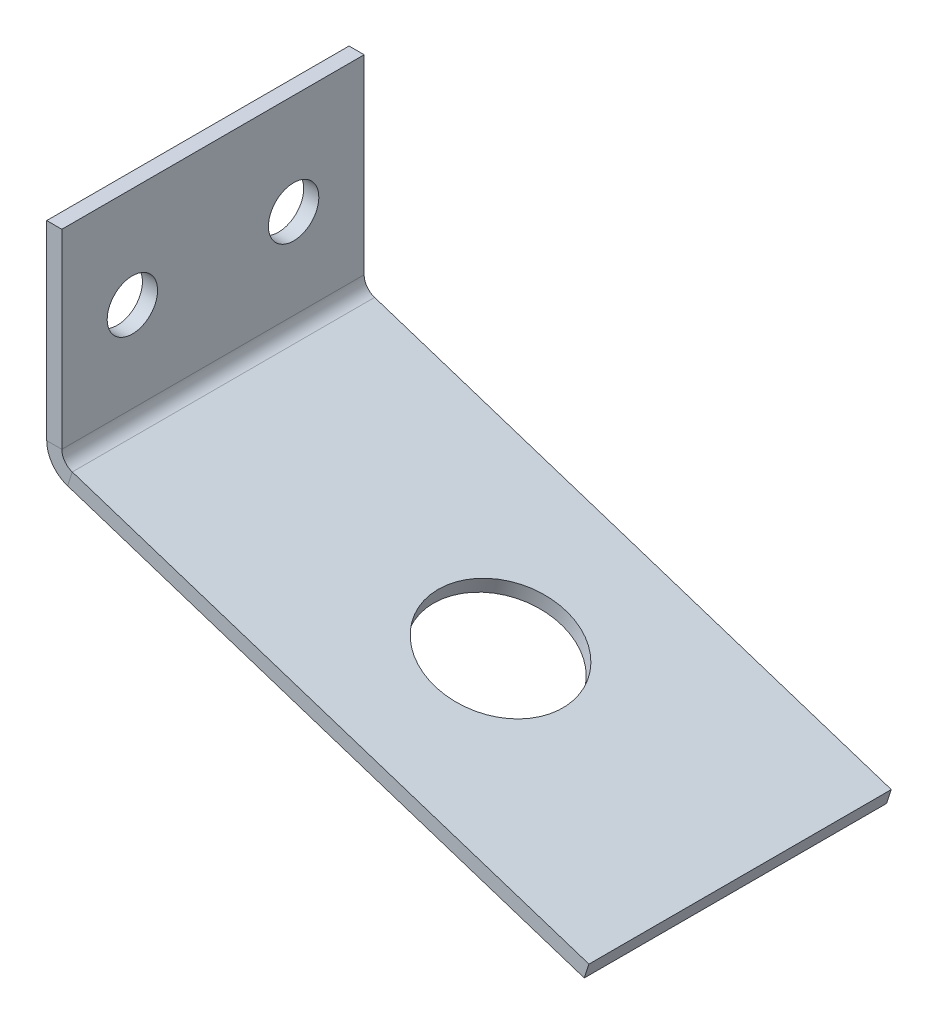
SolidWorks part; units mm, degrees
note: The reader was unsure of these and kept them because the rebuilt part matched: bend radius of "Основание1".
ref_plane "Спереди" through (0, 0, 0) normal (0, 0, 1) x (1, 0, 0)
ref_plane "Сверху" through (0, 0, 0) normal (0, 1, 0) x (1, 0, 0)
ref_plane "Справа" through (0, 0, 0) normal (1, 0, 0) x (0, 0, -1)
sketch "Эскиз1" plane through (0, 0, 0) normal (0, 0, 1) x (1, 0, 0)
  line L0 (0, 20) -> (0, 0)
  line L1 (0, 0) -> (52.3081, -16.9959)
  dimension "D1" = 20
  dimension "D2" = 108
  dimension "D3" = 55
base flange "Базовая кромка1" sketch "Эскиз1" end condition mid plane depth 30 reverse direction no thickness 1.5 reverse thickness direction no bend radius 1.5
bend "Основание1" bend radius 1.5 bend angle 72 parameters "D5"=1
sketch "Эскиз6" plane through (0, 0, 0) normal (1, 0, 0) x (0, 0, -1)
  line L0 (-15, 20) -> (15, 20) construction
  line L1 (15, 20) -> (15, 1.0898) construction
  circle A0 centre (-8, 10) radius 2.5
  circle A1 centre (8, 10) radius 2.5
  dimension "D1" = 10
  dimension "D2" = 7
  dimension "D3" = 5
  dimension "D4" = 16
extrude "крепление" cut sketch "Эскиз6" against normal blind 10
sketch "Эскиз7" plane through (0, 0, 0) normal (0.309, 0.9511, 0) x (0.9511, -0.309, 0)
  line L0 (55, -15) -> (55, 15) construction
  line L1 (1.0898, -15) -> (55, -15) construction
  circle A0 centre (30, 0) radius 6.5
  dimension "D1" = 25
  dimension "D2" = 13
  dimension "D3" = 15
extrude "Вырез-Вытянуть2" cut sketch "Эскиз7" against normal blind 10
sketch "Сгиб-Линии1" [suppressed] plane through (0, 0, 0) normal (0, 1, 0) x (1, 0, 0)
sketch "Граничная рамка1" [suppressed] plane through (0, 0, 0) normal (0, 1, 0) x (1, 0, 0)
sheet metal parameters "Листовой металл3" thickness 1.5 parameters "D1"=1.5
flat pattern "Развертка3" [suppressed]
sketch "Сгиб-Линии2" plane through (0, 0, 0) normal (0, 1, 0) x (1, 0, 0)
sketch "Граничная рамка2" [suppressed] plane through (0, 0, 0) normal (0, 1, 0) x (1, 0, 0)
bend of the flat pattern "Плоское состояние-<Основание1>1"
sheet metal parameters "Листовой металл4" thickness 1.5 parameters "D1"=1.5
flat pattern "Развертка3" [suppressed]
sketch "Сгиб-Линии2" plane through (0, 0, 0) normal (0, 1, 0) x (1, 0, 0)
sketch "Граничная рамка2" [suppressed] plane through (0, 0, 0) normal (0, 1, 0) x (1, 0, 0)
bend of the flat pattern "Плоское состояние-<Основание1>1"
sheet metal parameters "Листовой металл5" thickness 1.5 parameters "D1"=1.5
flat pattern "Развертка3"
sketch "Сгиб-Линии2" plane through (0, 0, 0) normal (1, 0, 0) x (0, 0, -1)
  line L0 (15, -0.3239) -> (-15, -0.3239) construction
  line L1 (15, -0.3239) -> (-15, -0.3239) construction
sketch3d "Граничная рамка2" [suppressed]
  line L0 (30, -75.6478, 0) -> (30, 0, 0) construction
  line L1 (0, -75.6478, 0) -> (0, 0, 0) construction
  line L2 (30, -75.6478, 0) -> (0, -75.6478, 0) construction
  line L3 (30, 0, 0) -> (0, 0, 0) construction
bend of the flat pattern "Плоское состояние-<Основание1>1"
